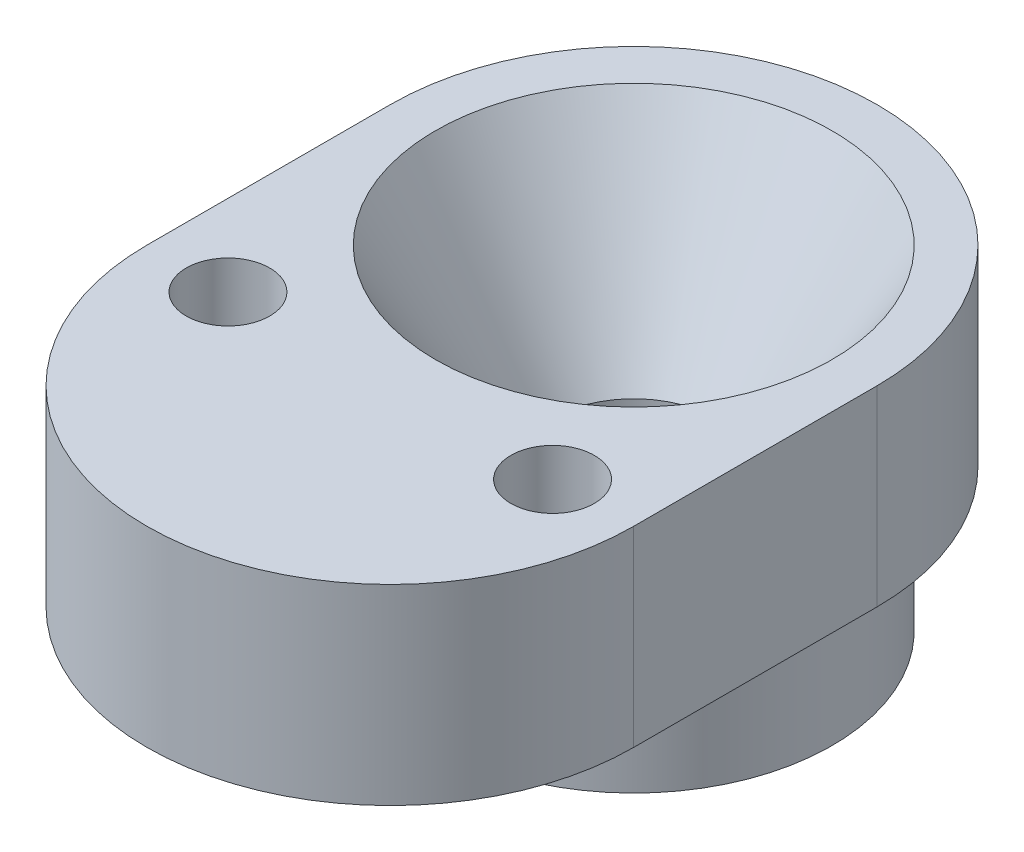
SolidWorks part; units mm, degrees
note: The reader was unsure of these and kept them because the rebuilt part matched: shared geometry of "上视标记<4>".
ref_plane "前视基准面" through (0, 0, 0) normal (0, 0, 1) x (1, 0, 0)
ref_plane "上视基准面" through (0, 0, 0) normal (0, 1, 0) x (1, 0, 0)
ref_plane "右视基准面" through (0, 0, 0) normal (1, 0, 0) x (0, 0, -1)
sketch "前视标记" plane through (0, 0, 0) normal (0, 0, 1) x (1, 0, 0)
  line L0 (1.524, 0) -> (17.526, 0)
  line L1 (17.526, 0) -> (17.526, 5.588)
  line L2 (17.526, 5.588) -> (19.05, 5.588)
  line L3 (19.05, 5.588) -> (19.05, 13.081)
  line L4 (19.05, 13.081) -> (0, 13.081)
  line L5 (0, 13.081) -> (0, 5.588)
  line L6 (0, 5.588) -> (1.524, 5.588)
  line L7 (1.524, 5.588) -> (1.524, 0)
  line L8 (1.524, 5.588) -> (17.526, 5.588)
  line L9 (9.525, 13.081) -> (9.525, 0) construction
  point P4 (9.525, 13.081)
  dimension "D1" = 7.493
  dimension "D2" = 5.588
  dimension "D3" = 16.002
  dimension "D4" = 19.05
sketch "上视标记" plane through (0, 0, 0) normal (0, 1, 0) x (1, 0, 0)
  line L0 (9.525, 0) -> (9.525, -19.05) construction
  line L1 (0, -9.525) -> (0, -19.05)
  line L2 (19.05, -9.525) -> (19.05, -19.05)
  arc A0 (19.05, -9.525) -> (0, -9.525) centre (9.525, -9.525) ccw
  arc A1 (0, -19.05) -> (19.05, -19.05) centre (9.525, -19.05) ccw
  circle A2 centre (9.525, -9.525) radius 7.7589
  circle A3 centre (9.525, -9.525) radius 3.237
  circle A4 centre (3.175, -19.05) radius 1.6319
  circle A5 centre (15.875, -19.05) radius 1.6319
  dimension "D3" = 3.2639
  dimension "D4" = 3.2639
  dimension "D5" = 15.5179
  dimension "D6" = 9.525
  dimension "D1" = 3.175
  dimension "D2" = 3.175
  dimension "D7" = 19.05
sketch "右视标记" plane through (0, 0, 0) normal (1, 0, 0) x (0, 0, -1)
  line L1 (-28.575, 13.081) -> (0, 13.081)
  line L2 (-28.575, 13.081) -> (-28.575, 5.588)
  line L3 (-28.575, 5.588) -> (0, 5.588)
  line L4 (0, 13.081) -> (0, 5.588)
  line L5 (-1.524, 0) -> (-17.526, 0)
  line L6 (-1.524, 0) -> (-1.524, 5.588)
  line L7 (-1.524, 5.588) -> (-17.526, 5.588)
  line L8 (-17.526, 0) -> (-17.526, 5.588)
  dimension "D1" = 28.575
  dimension "D2" = 7.493
  dimension "D3" = 16.002
extrude "主体" add sketch "上视标记" along normal up to vertex (13.081 mm away) separate body up to point (0, 13.081, 0)
extrude "拉伸3" cut sketch "上视标记<4>" along normal up to vertex (5.588 mm away)
sketch "上视标记<4>" plane through (0, 0, 0) normal (0, 1, 0) x (1, 0, 0) same geometry as "上视标记"
sketch "草图4" plane through (0, 13.081, 0) normal (0, 1, 0) x (1, 0, 0)
  line L2 (0, -9.525) -> (0, -19.05)
  line L3 (19.05, -19.05) -> (19.05, -9.525)
  line L4 (0, -9.525) -> (0, -19.05)
  line L5 (19.05, -19.05) -> (19.05, -9.525)
  circle A1 centre (9.525, -9.525) radius 3.237
  circle A2 centre (9.525, -9.525) radius 3.237
  circle A3 centre (9.525, -9.525) radius 7.7589
  circle A4 centre (9.525, -9.525) radius 7.7589
  circle A5 centre (15.875, -19.05) radius 1.6319
  arc A6 (0, -19.05) -> (19.05, -19.05) centre (9.525, -19.05) ccw
  arc A7 (19.05, -9.525) -> (0, -9.525) centre (9.525, -9.525) ccw
  arc A8 (0, -19.05) -> (19.05, -19.05) centre (9.525, -19.05) ccw
  arc A9 (19.05, -9.525) -> (0, -9.525) centre (9.525, -9.525) ccw
  circle A10 centre (15.875, -19.05) radius 1.6319
  circle A11 centre (3.175, -19.05) radius 1.6319
  circle A12 centre (3.175, -19.05) radius 1.6319
  dimension "D1" = 0
  dimension "D2" = 0
  dimension "D3" = 0
  dimension "D4" = 0
  dimension "D5" = 0
sketch "草图5" plane through (0, 5.588, 0) normal (0, -1, 0) x (1, 0, 0)
  circle A0 centre (9.525, 9.525) radius 3.237 construction
  circle A1 centre (9.525, 9.525) radius 3.237
loft "切除-放样1" cut profiles "草图5" section "草图4" section "草图5" connector at (17.2783, 13.081, 9.8212) connector at (12.7596, 5.588, 9.3995)
